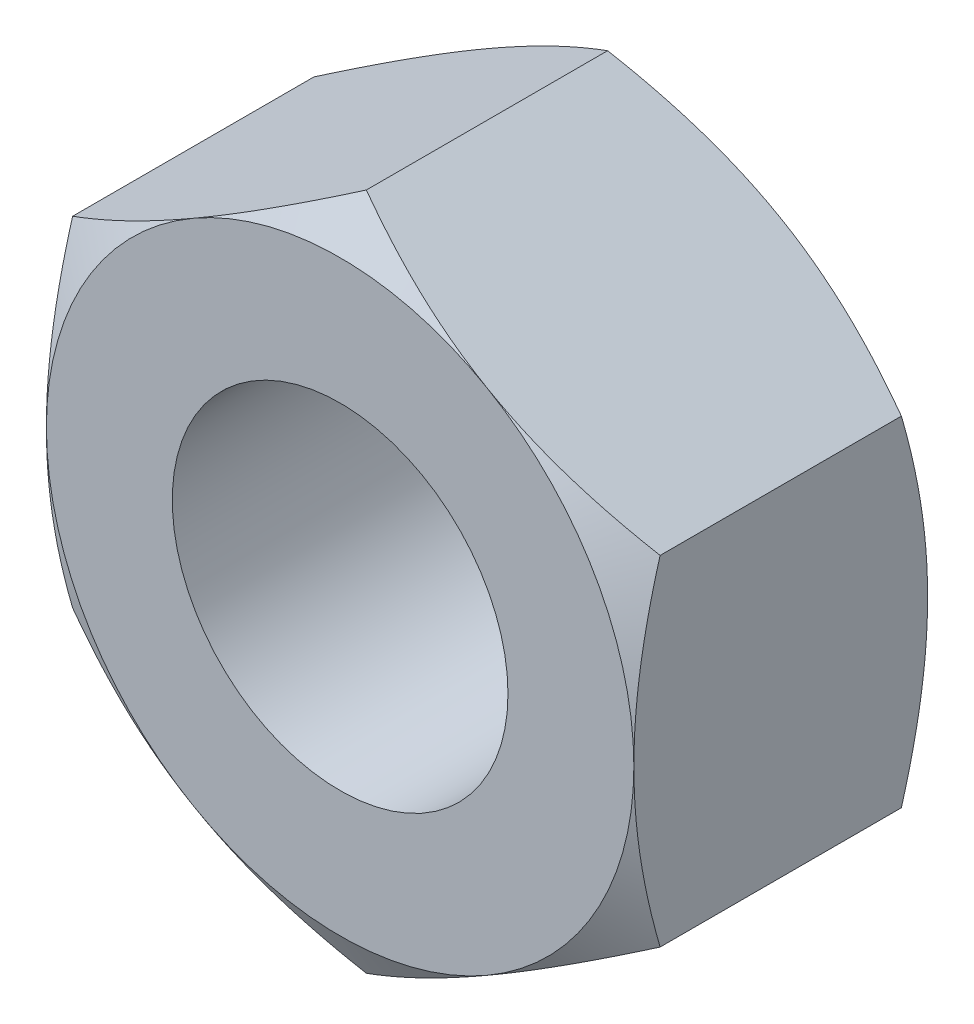
SolidWorks part; units mm, degrees
ref_plane "Front" through (0, 0, 0) normal (0, 0, 1) x (1, 0, 0)
ref_plane "Top" through (0, 0, 0) normal (0, 1, 0) x (1, 0, 0)
ref_plane "Right" through (0, 0, 0) normal (1, 0, 0) x (0, 0, -1)
sketch "Sketch1" plane through (0, 0, 0) normal (0, 0, 1) x (1, 0, 0)
  line L0 (0, 0) -> (-2.2451, 2.2451) construction
  line L1 (-5.5563, 3.2079) -> (-5.5563, -3.2079)
  line L2 (-5.5563, -3.2079) -> (0, -6.4158)
  line L3 (0, -6.4158) -> (5.5563, -3.2079)
  line L4 (5.5563, -3.2079) -> (5.5563, 3.2079)
  line L5 (5.5563, 3.2079) -> (0, 6.4158)
  line L6 (0, 6.4158) -> (-5.5563, 3.2079)
  line L7 (0, 0) -> (-3.175, 0) construction
  circle A0 centre (0, 0) radius 5.5562 construction
  circle A1 centre (0, 0) radius 3.175
  point P10 (0, 3.175)
  point P11 (0, -3.175)
  dimension "hex" = 11.1125
  dimension "dia" = 6.35
  dimension "D1" = 45
extrude "Extrude1" add sketch "Sketch1" along normal mid plane 5.5562
sketch "Sketch10" plane through (0, 0, 2.7781) normal (0, 0, 1) x (1, 0, 0)
  line L0 (0, 0) -> (-2.2451, 2.2451) construction
  line L1 (0, 0) -> (-2.2451, 2.2451)
sketch "Sketch9" plane through (0, 0, 2.7781) normal (0, 0, 1) x (1, 0, 0)
  circle A0 centre (0, 0) radius 5.5562 construction
  circle A1 centre (0, 0) radius 5.5562
extrude "Cut-Extrude2" cut sketch "Sketch9" against normal through all draft 60 flip side to cut
mirror "Mirror2" about plane through (0, 0, 0) normal (0, 0, 1) of "Cut-Extrude2"
sketch "Sketch4" [suppressed] plane through (0, 0, 2.7781) normal (0, 0, -1) x (-1, 0, 0)
  circle A0 centre (0, 0) radius 3.175 construction
  circle A1 centre (0, 0) radius 3.175
curve "Helix/Spiral3" [suppressed] pitch 1.27 height 6.8262 turns 5.375
sketch "Sketch3" [suppressed] plane through (0, 0, 0) normal (1, 0, 0) x (0, 0, -1)
  line L0 (-3.8894, 3.175) -> (-2.7781, 3.175)
  line L1 (-2.7781, 3.175) -> (-3.2544, 2.3501)
  line L2 (-3.2544, 2.3501) -> (-3.4131, 2.3501)
  line L3 (-3.4131, 2.3501) -> (-3.8894, 3.175)
  line L4 (-3.6513, 2.7626) -> (-3.0162, 2.7626) construction
  line L5 (-2.7781, 3.175) -> (-2.7781, -3.175) construction
  dimension "D1" = 60
  dimension "D2" = 0.635
  dimension "D3" = 0.1588
sweep "Sweep1" [suppressed] add profiles "Sketch3" path "Helix/Spiral3"
sketch "Sketch8" [suppressed] plane through (0, 0, 2.7781) normal (0, 0, 1) x (1, 0, 0)
  circle A1 centre (0, 0) radius 3.175
  circle A2 centre (0, 0) radius 3.175
  dimension "D1" = 0
extrude "Cut-Extrude1" [suppressed] cut sketch "Sketch8" along normal through all and the other way through all draft 45
sketch "Sketch11" [suppressed] plane through (0, 0, -2.7781) normal (0, 0, -1) x (-1, 0, 0)
  circle A1 centre (0, 0) radius 3.175
  circle A2 centre (0, 0) radius 3.175
  dimension "D1" = 0
extrude "Cut-Extrude3" [suppressed] cut sketch "Sketch11" along normal through all
sketch "Sketch13" [suppressed] plane through (0, 0, -2.7781) normal (0, 0, -1) x (-1, 0, 0)
  circle A1 centre (0, 0) radius 3.175
  circle A2 centre (0, 0) radius 3.175
  dimension "D1" = 0
extrude "Cut-Extrude7" [suppressed] cut sketch "Sketch13" against normal through all draft 45
sketch "Sketch14" [suppressed] plane through (0, 0, 2.7781) normal (0, 0, 1) x (1, 0, 0)
  circle A2 centre (0, 0) radius 3.429
  dimension "D1" = 6.858
extrude "Cut-Extrude10" [suppressed] cut sketch "Sketch14" against normal through all draft 45
equation "\"D3@Helix/Spiral3\" = \"length@Extrude1\"+\"D4@Helix/Spiral3\""
equation "\"D2@Sketch3\" = \"D4@Helix/Spiral3\" * .5"
equation "\"D3@Sketch3\" = \"D4@Helix/Spiral3\" * .125"
equation "\"D1@Sketch14\"=\"dia@Sketch1\"*1.08"
